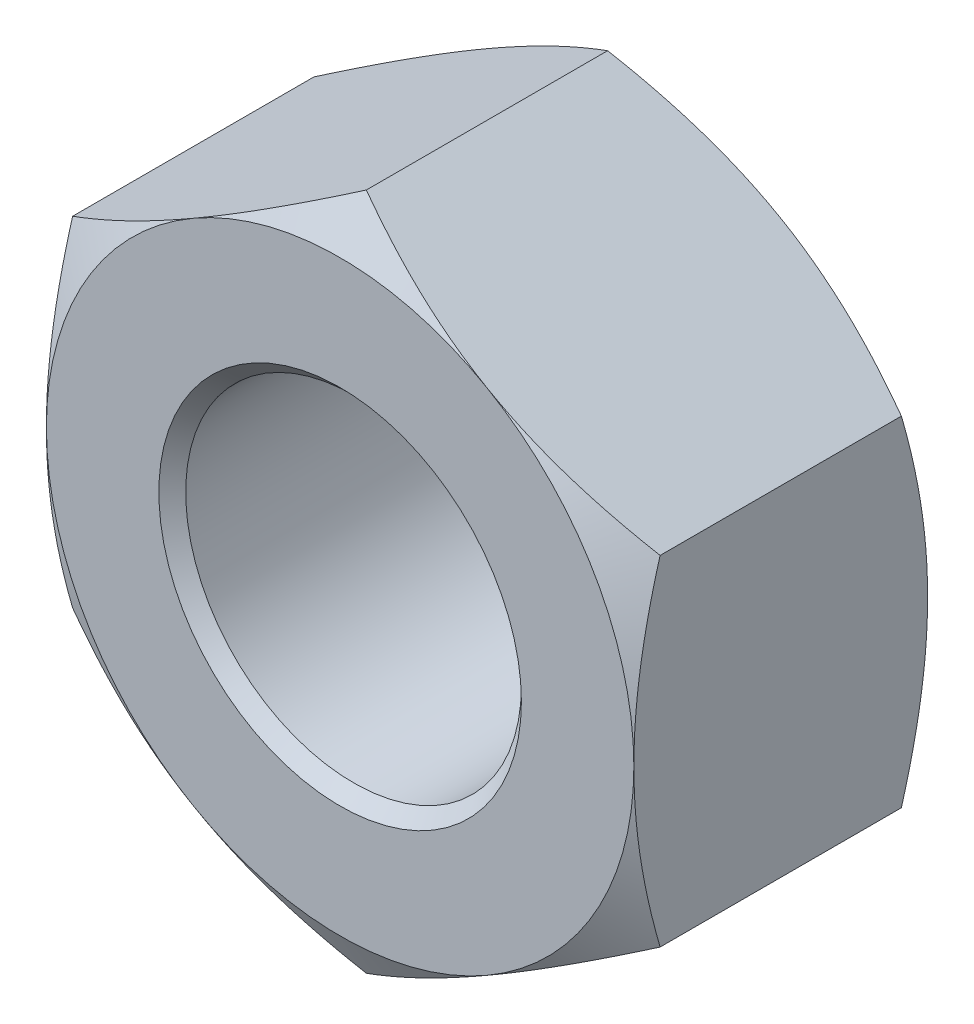
SolidWorks part; units mm, degrees
ref_plane "Front" through (0, 0, 0) normal (0, 0, 1) x (1, 0, 0)
ref_plane "Top" through (0, 0, 0) normal (0, 1, 0) x (1, 0, 0)
ref_plane "Right" through (0, 0, 0) normal (1, 0, 0) x (0, 0, -1)
sketch "Sketch1" plane through (0, 0, 0) normal (0, 0, 1) x (1, 0, 0)
  line L0 (0, 0) -> (-2.2451, 2.2451) construction
  line L1 (-5.5563, 3.2079) -> (-5.5563, -3.2079)
  line L2 (-5.5563, -3.2079) -> (0, -6.4158)
  line L3 (0, -6.4158) -> (5.5563, -3.2079)
  line L4 (5.5563, -3.2079) -> (5.5563, 3.2079)
  line L5 (5.5563, 3.2079) -> (0, 6.4158)
  line L6 (0, 6.4158) -> (-5.5563, 3.2079)
  line L7 (0, 0) -> (-3.175, 0) construction
  circle A0 centre (0, 0) radius 5.5562 construction
  circle A1 centre (0, 0) radius 3.175
  point P10 (0, 3.175)
  point P11 (0, -3.175)
  dimension "hex" = 11.1125
  dimension "dia" = 6.35
  dimension "D1" = 45
extrude "Extrude1" add sketch "Sketch1" along normal mid plane 5.5562
sketch "Sketch10" plane through (0, 0, 2.7781) normal (0, 0, 1) x (1, 0, 0)
  line L0 (0, 0) -> (-2.2451, 2.2451) construction
  line L1 (0, 0) -> (-2.2451, 2.2451)
sketch "Sketch9" plane through (0, 0, 2.7781) normal (0, 0, 1) x (1, 0, 0)
  circle A0 centre (0, 0) radius 5.5562 construction
  circle A1 centre (0, 0) radius 5.5562
extrude "Cut-Extrude2" cut sketch "Sketch9" against normal through all draft 60 flip side to cut
mirror "Mirror2" about plane through (0, 0, 0) normal (0, 0, 1) of "Cut-Extrude2"
sketch "Sketch4" plane through (0, 0, 2.7781) normal (0, 0, -1) x (-1, 0, 0)
  circle A0 centre (0, 0) radius 3.175 construction
  circle A1 centre (0, 0) radius 3.175
curve "Helix/Spiral3" [suppressed] pitch 1.27 height 6.8262 turns 5.375
sketch "Sketch3" plane through (0, 0, 0) normal (1, 0, 0) x (0, 0, -1)
  line L0 (-3.8894, 3.175) -> (-2.7781, 3.175)
  line L1 (-2.7781, 3.175) -> (-3.2544, 2.3501)
  line L2 (-3.2544, 2.3501) -> (-3.4131, 2.3501)
  line L3 (-3.4131, 2.3501) -> (-3.8894, 3.175)
  line L4 (-3.6513, 2.7626) -> (-3.0162, 2.7626) construction
  line L5 (-2.7781, 3.175) -> (-2.7781, -3.175) construction
  dimension "D1" = 60
  dimension "D2" = 0.635
  dimension "D3" = 0.1588
sweep "Sweep1" [suppressed] add profiles "Sketch3" path "Helix/Spiral3"
sketch "Sketch8" plane through (0, 0, 2.7781) normal (0, 0, 1) x (1, 0, 0)
  circle A1 centre (0, 0) radius 3.175
  circle A2 centre (0, 0) radius 3.175
  dimension "D1" = 0
extrude "Cut-Extrude1" [suppressed] cut sketch "Sketch8" along normal through all and the other way through all draft 45
sketch "Sketch11" plane through (0, 0, -2.7781) normal (0, 0, -1) x (-1, 0, 0)
  circle A1 centre (0, 0) radius 3.175
  circle A2 centre (0, 0) radius 3.175
  dimension "D1" = 0
extrude "Cut-Extrude3" [suppressed] cut sketch "Sketch11" along normal through all
sketch "Sketch13" plane through (0, 0, -2.7781) normal (0, 0, -1) x (-1, 0, 0)
  circle A1 centre (0, 0) radius 3.175
  circle A2 centre (0, 0) radius 3.175
  dimension "D1" = 0
extrude "Cut-Extrude7" [suppressed] cut sketch "Sketch13" against normal through all draft 45
sketch "Sketch14" plane through (0, 0, 2.7781) normal (0, 0, 1) x (1, 0, 0)
  circle A2 centre (0, 0) radius 3.429
  dimension "D1" = 6.858
extrude "Cut-Extrude10" cut sketch "Sketch14" against normal through all draft 45
equation "\"D3@Helix/Spiral3\" = \"length@Extrude1\"+\"D4@Helix/Spiral3\""
equation "\"D2@Sketch3\" = \"D4@Helix/Spiral3\" * .5"
equation "\"D3@Sketch3\" = \"D4@Helix/Spiral3\" * .125"
equation "\"D1@Sketch14\"=\"dia@Sketch1\"*1.08"
